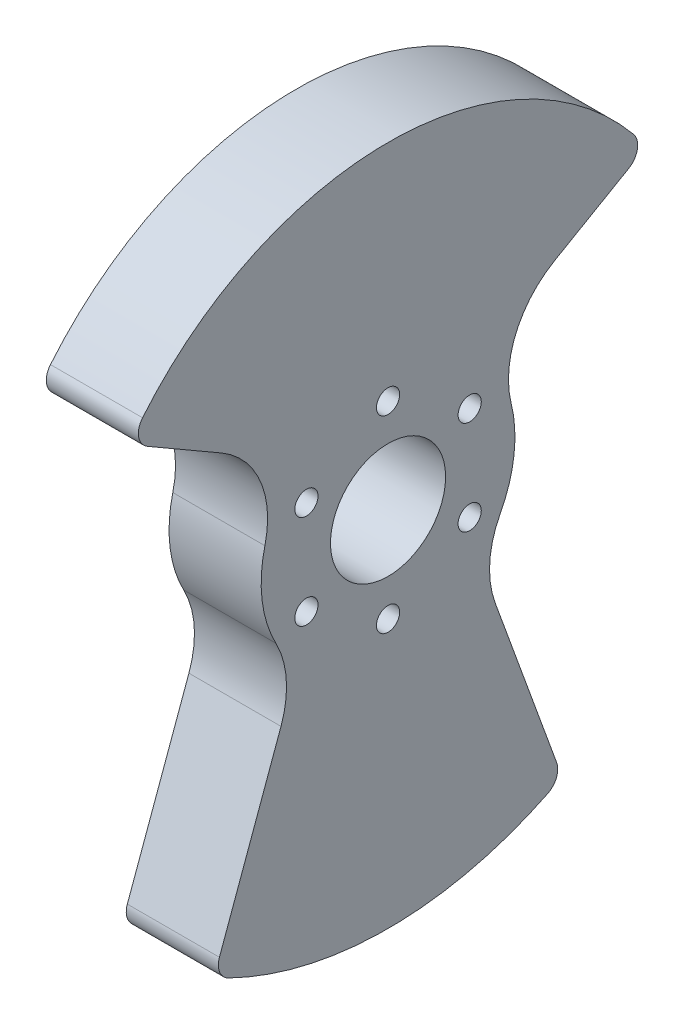
SolidWorks part; units mm, degrees
material "Alloy Steel"
ref_plane "Front Plane" through (0, 0, 0) normal (0, 0, 1) x (1, 0, 0)
ref_plane "Top Plane" through (0, 0, 0) normal (0, 1, 0) x (1, 0, 0)
ref_plane "Right Plane" through (0, 0, 0) normal (1, 0, 0) x (0, 0, -1)
other "Center of Mass"
sketch "Sketch1" plane through (0, 0, 0) normal (1, 0, 0) x (0, 0, -1)
  line L0 (-48.0121, -87.7202) -> (-25, -24.4949)
  line L1 (0, 0) -> (0, 87.8) construction
  line L2 (48.0121, -87.7202) -> (25, -24.4949)
  line L3 (-71.3051, 51.2291) -> (-25, 24.4949)
  line L4 (71.3051, 51.2291) -> (25, 24.4949)
  line L6 (-76.2, -152.4) -> (76.2, -152.4) construction
  line L7 (-76.2, -152.4) -> (-76.2, 152.4) construction
  line L8 (-76.2, 152.4) -> (76.2, 152.4) construction
  line L9 (76.2, -152.4) -> (76.2, 152.4) construction
  line L10 (-76.2, -152.4) -> (76.2, 152.4) construction
  line L11 (-76.2, 152.4) -> (76.2, -152.4) construction
  circle A0 centre (0, 0) radius 15.875
  arc A1 (-48.0121, -87.7202) -> (48.0121, -87.7202) centre (0, 0) ccw
  arc A2 (-71.3051, 51.2291) -> (71.3051, 51.2291) centre (0, 0) cw
  arc A3 (-25, 24.4949) -> (-25, -24.4949) centre (0, 0) ccw
  arc A4 (25, -24.4949) -> (25, 24.4949) centre (0, 0) ccw
  dimension "D1" = 31.75
  dimension "D2" = 70
  dimension "D3" = 100
  dimension "D4" = 87.8
  dimension "D6" = 120
  dimension "D9" = 152.4
  dimension "D5" = 40
  dimension "D7" = 50
  dimension "D8" = 304.8
extrude "Boss-Extrude1" add sketch "Sketch1" along normal mid plane 25.4 contours A0 A2 L3 A3 L0 A1 L2 A4 L4 region at (0, -56.9141, 34.2902)
fillet "Fillet2" radius 25.4 4 edges at (0, -24.4949, 25) (0, 24.4949, 25) (0, -24.4949, -25) (0, 24.4949, -25)
fillet "Fillet3" radius 5 4 edges at (0, -87.7202, 48.0121) (0, 51.2291, 71.3051) (0, -87.7202, -48.0121) (0, 51.2291, -71.3051)
sketch "Sketch2" plane through (0, 0, 0) normal (1, 0, 0) x (0, 0, -1)
  point P0 (0, -26)
  point P4 (-22.5167, -13)
  point P5 (-22.5167, 13)
  point P6 (0, 26)
  point P7 (22.5167, 13)
  point P8 (22.5167, -13)
  point P9 (0, 0)
  dimension "D2" = 52
  dimension "D1" = 6
hole_wizard "M6 Clearance Hole1" positions "Sketch3" profile "Sketch4" hole size "M6" standard "ANSI Metric" end condition up to next
sketch "Sketch3" plane through (-12.7, 0, 0) normal (-1, 0, 0) x (0, 0, 1)
  point P0 (-22.5167, 13)
  point P3 (0, 26)
  point P6 (22.5167, 13)
  point P9 (22.5167, -13)
  point P12 (0, -26)
  point P15 (-22.5167, -13)
sketch "Sketch4" plane through (-12.7, 13, -22.5167) normal (0, 1, 0) x (0, 0, 1)
  line L0 (0, 0) -> (0, 25.4)
  line L1 (0, 25.4) -> (3.2, 25.4)
  line L2 (3.2, 25.4) -> (3.2, 0)
  line L5 (3.2, 0) -> (0, 0)
  line L11 (0, -6.35) -> (0, 107.95) construction
  dimension "Thru Hole Dia." = 6.4
  dimension "Thru Hole Depth" = 25.4
